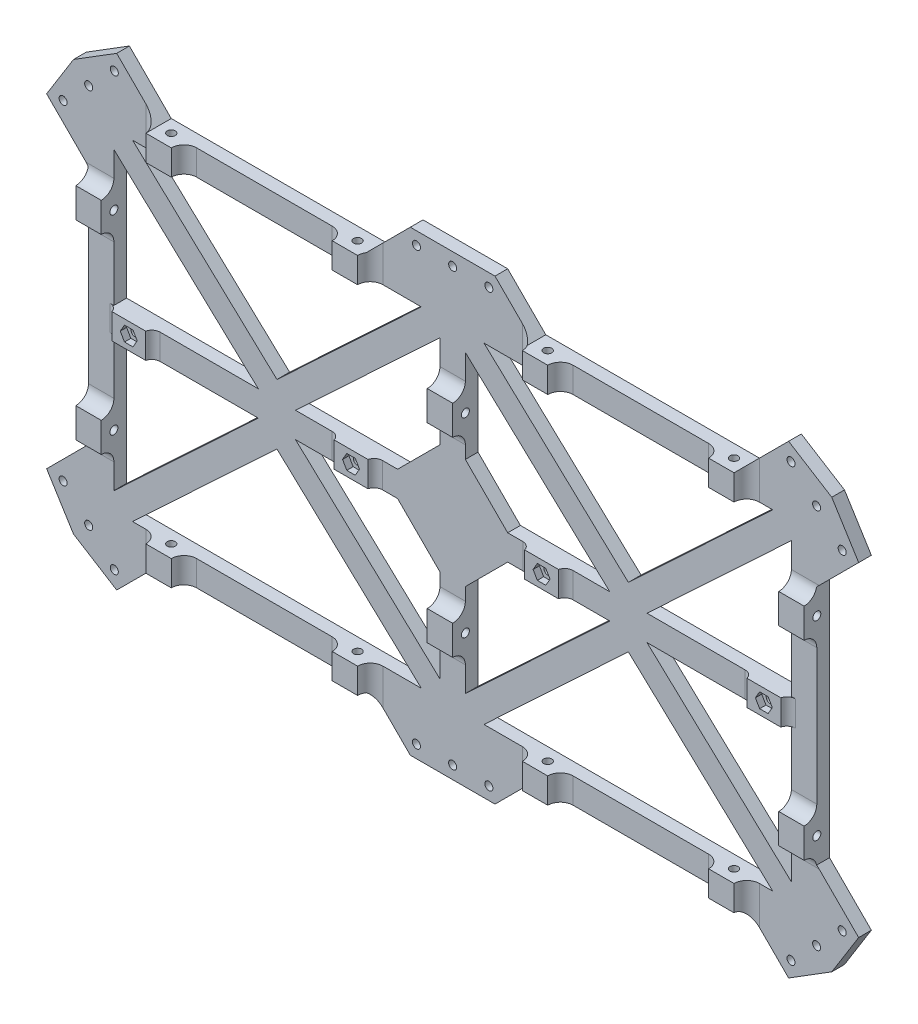
SolidWorks part; units mm, degrees
ref_plane "Plan de face" through (0, 0, 0) normal (0, 0, 1) x (1, 0, 0)
ref_plane "Plan de dessus" through (0, 0, 0) normal (0, 1, 0) x (1, 0, 0)
ref_plane "Plan de droite" through (0, 0, 0) normal (1, 0, 0) x (0, 0, -1)
sketch "Esquisse1" plane through (0, 0, 0) normal (0, 0, 1) x (1, 0, 0)
  line L0 (-86, 45) -> (86, 45)
  line L1 (-75.6076, 39) -> (-7.3924, 39)
  line L2 (-80, 34.8928) -> (-80, 3)
  line L3 (-75.6076, -39) -> (-7.3924, -39)
  line L4 (80, 34.8928) -> (80, 3)
  line L5 (86, 45) -> (86, -45)
  line L6 (-86, -45) -> (86, -45)
  line L7 (-86, 45) -> (-86, -45)
  line L8 (-80, 0) -> (80, 0) construction
  line L9 (-80, 3) -> (-45.8924, 3)
  line L10 (-3, -34.8928) -> (-3, -3)
  line L11 (0, 39) -> (0, -39) construction
  line L12 (-3, 34.8928) -> (-3, 3)
  line L13 (-37.1076, -3) -> (-3, -3)
  line L14 (-10, 45) -> (-10, 39) construction
  line L15 (10, 45) -> (10, 39) construction
  line L16 (-80, 39) -> (-41.5, 3) construction
  line L17 (-60.75, 21) -> (-58.701, 23.1913) construction
  line L18 (-58.701, 23.1913) -> (-75.6076, 39)
  line L19 (-80, -3) -> (-45.8924, -3)
  line L20 (-60.75, -21) -> (-62.799, -18.8087) construction
  line L21 (-60.75, -21) -> (-58.701, -23.1913) construction
  line L22 (-80, -39) -> (-41.5, -3) construction
  line L23 (-58.8571, 23.3372) -> (-41.5, 7.1072)
  line L24 (-60.75, 21) -> (-62.799, 18.8087) construction
  line L25 (-62.799, 18.8087) -> (-80, 34.8928)
  line L26 (-62.799, 18.8087) -> (-45.8924, 3)
  line L27 (-37.1076, 3) -> (-3, 3)
  line L28 (-62.799, -18.8087) -> (-45.8924, -3)
  line L29 (-62.799, -18.8087) -> (-80, -34.8928)
  line L30 (-58.8571, -23.3372) -> (-41.5, -7.1072)
  line L31 (-58.701, -23.1913) -> (-75.6076, -39)
  line L32 (3, 34.8928) -> (3, 3)
  line L33 (3, -34.8928) -> (3, -3)
  line L34 (80, -39) -> (41.5, -3) construction
  line L35 (60.75, -21) -> (58.701, -23.1913) construction
  line L36 (60.75, -21) -> (62.799, -18.8087) construction
  line L37 (58.701, -23.1913) -> (75.6076, -39)
  line L38 (58.8571, -23.3372) -> (41.5, -7.1072)
  line L39 (62.799, -18.8087) -> (80, -34.8928)
  line L40 (62.799, -18.8087) -> (45.8924, -3)
  line L41 (80, -3) -> (45.8924, -3)
  line L42 (37.1076, -3) -> (3, -3)
  line L43 (37.1076, 3) -> (3, 3)
  line L44 (80, 3) -> (45.8924, 3)
  line L45 (60.75, 21) -> (62.799, 18.8087) construction
  line L46 (60.75, 21) -> (58.701, 23.1913) construction
  line L47 (80, 39) -> (41.5, 3) construction
  line L48 (62.799, 18.8087) -> (45.8924, 3)
  line L49 (62.799, 18.8087) -> (80, 34.8928)
  line L50 (58.8571, 23.3372) -> (41.5, 7.1072)
  line L51 (58.701, 23.1913) -> (75.6076, 39)
  line L52 (7.3924, -39) -> (75.6076, -39)
  line L53 (7.3924, 39) -> (75.6076, 39)
  line L54 (-80, -39) -> (80, -39) construction
  line L55 (-80, -3) -> (-80, -34.8928)
  line L56 (-80, 39) -> (80, 39) construction
  line L57 (80, -3) -> (80, -34.8928)
  line L58 (-80, 39) -> (-80, -39) construction
  line L59 (-3, 39) -> (-41.5, 3) construction
  line L60 (80, 39) -> (80, -39) construction
  line L61 (-36.5997, 7.5821) -> (-34.5507, 5.3908) construction
  line L62 (-36.5997, 7.5821) -> (-38.6487, 9.7734) construction
  line L63 (-34.5507, 5.3908) -> (-3, 34.8928)
  line L64 (-34.5507, 5.3908) -> (-37.1076, 3)
  line L65 (-34.5507, 5.3908) -> (-37.1076, 3)
  line L66 (-34.5507, 5.3908) -> (-37.1076, 3)
  line L67 (-41.5, -3) -> (-3, -39) construction
  line L68 (-41.5, 7.1072) -> (-7.3924, 39)
  line L69 (-37.1076, -3) -> (-3, -34.8928)
  line L70 (41.5, -3) -> (3, -39) construction
  line L71 (41.5, -7.1072) -> (7.3924, -39)
  line L72 (-41.5, -7.1072) -> (-7.3924, -39)
  line L73 (37.1076, -3) -> (3, -34.8928)
  line L74 (3, 39) -> (41.5, 3) construction
  line L75 (41.5, 7.1072) -> (7.3924, 39)
  line L76 (34.5507, 5.3908) -> (3, 34.8928)
  line L77 (34.5507, 5.3908) -> (37.1076, 3)
  dimension "D6" = 3
  dimension "D1" = 78
  dimension "D2" = 160
  dimension "D3" = 80
  dimension "D4" = 39
  dimension "D7" = 3
  dimension "D8" = 3
  dimension "D9" = 3
  dimension "D10" = 10
  dimension "D11" = 10
  dimension "D12" = 3
  dimension "D13" = 38.5
  dimension "D14" = 3
  dimension "D15" = 3
  dimension "D5" = 6
extrude "Boss.-Extru.1" add sketch "Esquisse1" along normal blind 3 contours L0 L7 L6 L5 L55 L19 L28 L29 L52 L33 L42 L38 L37 L31 L30 L13 L10 L3 L27 L23 L18 L1 L12 L25 L26 L9 L2 L48 L49 L4 L44 L32 L53 L51 L50 L43 L41 L57 L39 region at (0, 0, 0)
sketch "Esquisse2" plane through (0, 0, 3) normal (0, 0, 1) x (1, 0, 0)
  line L0 (-13, -3) -> (-3, -13)
  line L1 (-37.1076, -3) -> (-3, -3) construction
  line L2 (-3, -34.8928) -> (-3, -3) construction
  line L3 (-13, -3) -> (-13, 3)
  line L4 (-37.1076, 3) -> (-3, 3) construction
  line L5 (-13, 3) -> (-3, 13)
  line L6 (-3, 34.8928) -> (-3, 3) construction
  line L7 (-3, 13) -> (3, 13)
  line L8 (3, 34.8928) -> (3, 3) construction
  line L9 (3, 13) -> (13, 3)
  line L10 (37.1076, 3) -> (3, 3) construction
  line L11 (13, 3) -> (13, -3)
  line L12 (37.1076, -3) -> (3, -3) construction
  line L13 (13, -3) -> (3, -13)
  line L14 (3, -34.8928) -> (3, -3) construction
  line L15 (3, -13) -> (-3, -13)
  line L16 (0, 45) -> (0, -45) construction
  line L17 (-86, 45) -> (86, 45) construction
  line L18 (-86, -45) -> (86, -45) construction
  line L19 (-10.3, 45) -> (-10.3, 39)
  line L20 (-75.6076, 39) -> (-7.3924, 39) construction
  line L21 (10.3, 45) -> (10.3, 39)
  line L22 (7.3924, 39) -> (75.6076, 39) construction
  line L23 (0, 45) -> (0, 54) construction
  line L24 (-11.55, 39) -> (-11.55, 45) construction
  line L25 (0, 54) -> (-10, 54)
  line L26 (0, 54) -> (10, 54)
  line L27 (10, 54) -> (19, 45)
  line L28 (-10, 54) -> (-19, 45)
  line L29 (-86, 0) -> (86, 0) construction
  line L30 (-86, 45) -> (-86, -45) construction
  line L31 (86, 45) -> (86, -45) construction
  line L32 (10, -54) -> (19, -45)
  line L33 (-10, -54) -> (-19, -45)
  line L34 (0, -54) -> (10, -54)
  line L35 (0, -54) -> (-10, -54)
  line L36 (-86, 45) -> (-110.1085, 69.1085) construction
  line L37 (-85.9542, 44.9542) -> (-99.2144, 31.694) construction
  line L38 (-85.9542, 44.9542) -> (-79.9085, 51) construction
  line L39 (-79.3417, 54.888) -> (-69.4537, 45)
  line L40 (-89.5355, 48.5355) -> (-79.3417, 54.888)
  line L41 (-95.888, 38.3417) -> (-86, 28.4537)
  line L42 (-89.5355, 48.5355) -> (-95.888, 38.3417)
  line L43 (79.3417, 54.888) -> (69.4537, 45)
  line L44 (89.5355, 48.5355) -> (79.3417, 54.888)
  line L45 (89.5355, 48.5355) -> (95.888, 38.3417)
  line L46 (95.888, 38.3417) -> (86, 28.4537)
  line L47 (95.888, -38.3417) -> (86, -28.4537)
  line L48 (89.5355, -48.5355) -> (95.888, -38.3417)
  line L49 (89.5355, -48.5355) -> (79.3417, -54.888)
  line L50 (79.3417, -54.888) -> (69.4537, -45)
  line L51 (-79.3417, -54.888) -> (-69.4537, -45)
  line L52 (-89.5355, -48.5355) -> (-79.3417, -54.888)
  line L53 (-89.5355, -48.5355) -> (-95.888, -38.3417)
  line L54 (-95.888, -38.3417) -> (-86, -28.4537)
  circle A0 centre (8.55, 51) radius 0.95
  circle A1 centre (-8.55, 51) radius 0.95
  circle A2 centre (0, 51) radius 0.95
  circle A3 centre (8.55, -51) radius 0.95
  circle A4 centre (-8.55, -51) radius 0.95
  circle A5 centre (0, -51) radius 0.95
  circle A6 centre (-85.9542, 44.9542) radius 0.95
  circle A7 centre (-92, 38.9085) radius 0.95
  circle A8 centre (-79.9085, 51) radius 0.95
  circle A9 centre (79.9085, 51) radius 0.95
  circle A10 centre (92, 38.9085) radius 0.95
  circle A11 centre (85.9542, 44.9542) radius 0.95
  circle A12 centre (92, -38.9085) radius 0.95
  circle A13 centre (85.9542, -44.9542) radius 0.95
  circle A14 centre (79.9085, -51) radius 0.95
  circle A15 centre (-79.9085, -51) radius 0.95
  circle A16 centre (-85.9542, -44.9542) radius 0.95
  circle A17 centre (-92, -38.9085) radius 0.95
  point P36 (-10.3, 42)
  line M19 (3, -34.8928) -> (3, -3)
  line M20 (3, -3) -> (37.1076, -3)
  line M23 (-37.1076, -3) -> (-3, -3)
  line M24 (-3, -3) -> (-3, -34.8928)
  line M26 (-3, 3) -> (-37.1076, 3)
  line M29 (-3, 34.8928) -> (-3, 3)
  line M30 (86, 45) -> (-86, 45)
  line M31 (-86, 45) -> (-86, -45)
  line M32 (-86, -45) -> (86, -45)
  line M33 (86, -45) -> (86, 45)
  line M40 (3, 3) -> (3, 34.8928)
  line M43 (37.1076, 3) -> (3, 3)
  dimension "D5" = 1.75
  dimension "D6" = 1.9
  dimension "D7" = 1.9
  dimension "D11" = 1.9
  dimension "D23" = 8.55
  dimension "D24" = 1.9
  dimension "D25" = 1.9
  dimension "D27" = 1.9
  dimension "D28" = 90
  dimension "D1" = 10
  dimension "D2" = 10
  dimension "D3" = 10.3
  dimension "D4" = 10.3
  dimension "D8" = 1.75
  dimension "D9" = 3
  dimension "D10" = 3
  dimension "D12" = 3
  dimension "D13" = 9
  dimension "D14" = 3
  dimension "D15" = 10
  dimension "D16" = 10
  dimension "D17" = 45
  dimension "D18" = 45
  dimension "D19" = 135
  dimension "D20" = 90
  dimension "D21" = 3
  dimension "D22" = 8.55
  dimension "D26" = 8.55
  dimension "D29" = 45
  dimension "D30" = 3.15
  dimension "D31" = 0
  dimension "D32" = 5
extrude "Boss.-Extru.2" add sketch "Esquisse2" against normal up to surface (3 mm away) contours A6 L39 L40 L42 L41 A8 A7 M30 M31 | L25 L28 L27 L26 A2 A1 A0 M30 | A11 L46 L45 L44 L43 A9 A10 M30 M33 | A13 L50 L49 L48 L47 A14 A12 M32 M33 | L35 L34 L32 L33 A4 A3 A5 M32 | A16 L54 L53 L52 L51 A15 A17 M32 M31 | L0 M23 M24 | L13 M20 M19 | L9 M40 M43 | L5 M26 M29 region at (-6.3333, -6.3333, 3) region at (-6.3333, 6.3333, 3) region at (6.3333, -6.3333, 3) region at (6.3333, 6.3333, 3) region at (0, 48.9683, 3) region at (-77.2295, 45.3738, 3) region at (74.6621, 49.6797, 3) region at (-86.3738, -36.2295, 3) region at (90.6797, -33.6621, 3) region at (0, -48.9683, 3) up to face at (41.5, -28.3691, 0)
sketch "Esquisse3" plane through (0, 0, 3) normal (0, 0, 1) x (1, 0, 0)
  line L0 (0, 54) -> (0, -54) construction
  line L1 (-86, 0) -> (86, 0) construction
  circle A0 centre (-85.9542, 44.9542) radius 0.95
  circle A1 centre (85.9542, 44.9542) radius 0.95
  circle A2 centre (85.9542, -44.9542) radius 0.95
  circle A3 centre (-85.9542, -44.9542) radius 0.95
  dimension "D1" = 1.9
extrude "Enlèv. mat.-Extru.1" cut sketch "Esquisse3" against normal up to surface (3 mm away) up to face at (-14.0269, -13.4732, 0)
sketch "Esquisse4" plane through (0, 0, 3) normal (0, 0, 1) x (1, 0, 0)
  line L0 (-86, 28.4537) -> (-86, -28.4537) construction
  line L1 (-80, 3) -> (-45.8924, 3) construction
  line L2 (-37.1076, 3) -> (-13, 3) construction
  line L3 (0, 54) -> (0, -54) construction
  circle A0 centre (-22.5, 0) radius 0.95
  circle A1 centre (-75, 0) radius 0.95
  circle A2 centre (22.5, 0) radius 0.95
  circle A3 centre (75, 0) radius 0.95
  dimension "D1" = 52.5
  dimension "D2" = 1.9
  dimension "D3" = 1.9
  dimension "D4" = 11
  dimension "D5" = 3
  dimension "D6" = 3
extrude "Enlèv. mat.-Extru.2" cut sketch "Esquisse4" against normal up to next
sketch "Esquisse5" plane through (0, 0, 3) normal (0, 0, 1) x (1, 0, 0)
  line L0 (-22.5, 0.95) -> (-22.5, -0.95) construction
  line L1 (0, 54) -> (0, -54) construction
  line L2 (-75, 0.95) -> (-75, -0.95) construction
  line L3 (-80, 3) -> (-45.8924, 3) construction
  line L4 (-73, 0) -> (-74, 1.7321)
  line L5 (-20.5, 0) -> (-21.5, 1.7321)
  line L6 (-21.5, 1.7321) -> (-23.5, 1.7321)
  line L7 (-23.5, 1.7321) -> (-24.5, 0)
  line L8 (-24.5, 0) -> (-23.5, -1.7321)
  line L9 (-74, 1.7321) -> (-76, 1.7321)
  line L10 (-23.5, -1.7321) -> (-21.5, -1.7321)
  line L11 (-21.5, -1.7321) -> (-20.5, 0)
  line L12 (-37.1076, 3) -> (-13, 3) construction
  line L13 (-26.5, 3) -> (-18.5, 3)
  line L14 (-26.5, 3) -> (-26.5, -3)
  line L15 (-26.5, -3) -> (-18.5, -3)
  line L16 (-18.5, 3) -> (-18.5, -3)
  line L17 (-37.1076, -3) -> (-13, -3) construction
  line L18 (-76, 1.7321) -> (-77, 0)
  line L19 (-77, 0) -> (-76, -1.7321)
  line L20 (-76, -1.7321) -> (-74, -1.7321)
  line L21 (-74, -1.7321) -> (-73, 0)
  line L22 (-80, -3) -> (-45.8924, -3) construction
  line L23 (-79, 3) -> (-71, 3)
  line L24 (-79, 3) -> (-79, -3)
  line L25 (-79, -3) -> (-71, -3)
  line L26 (-71, 3) -> (-71, -3)
  line L27 (22.5, 0.95) -> (22.5, -0.95) construction
  line L28 (18.5, 3) -> (18.5, -3)
  line L29 (26.5, -3) -> (18.5, -3)
  line L30 (26.5, 3) -> (26.5, -3)
  line L31 (26.5, 3) -> (18.5, 3)
  line L32 (21.5, -1.7321) -> (20.5, 0)
  line L33 (23.5, -1.7321) -> (21.5, -1.7321)
  line L34 (24.5, 0) -> (23.5, -1.7321)
  line L35 (23.5, 1.7321) -> (24.5, 0)
  line L36 (21.5, 1.7321) -> (23.5, 1.7321)
  line L37 (20.5, 0) -> (21.5, 1.7321)
  line L38 (75, 0.95) -> (75, -0.95) construction
  line L39 (71, 3) -> (71, -3)
  line L40 (79, -3) -> (71, -3)
  line L41 (79, 3) -> (79, -3)
  line L42 (79, 3) -> (71, 3)
  line L43 (74, -1.7321) -> (73, 0)
  line L44 (76, -1.7321) -> (74, -1.7321)
  line L45 (77, 0) -> (76, -1.7321)
  line L46 (76, 1.7321) -> (77, 0)
  line L47 (74, 1.7321) -> (76, 1.7321)
  line L48 (73, 0) -> (74, 1.7321)
  circle A0 centre (-22.5, 0) radius 0.95 construction
  circle A1 centre (-75, 0) radius 1.7321 construction
  circle A2 centre (-22.5, 0) radius 1.7321 construction
  circle A3 centre (-75, 0) radius 0.95 construction
  circle A4 centre (22.5, 0) radius 1.7321 construction
  circle A5 centre (75, 0) radius 1.7321 construction
  dimension "D1" = 4
  dimension "D2" = 2
  dimension "D3" = 2
  dimension "D4" = 4
  dimension "D5" = 4
  dimension "D6" = 4
extrude "Boss.-Extru.3" add sketch "Esquisse5" along normal blind 1.5
fillet "Congé1" radius 2 8 edges at (18.5, 0, 3) (71, 0, 3) (26.5, 0, 3) (79, 0, 3) (-18.5, 0, 3) (-26.5, 0, 3) (-71, 0, 3) (-79, 0, 3)
sketch "Esquisse6" plane through (0, 0, 3) normal (0, 0, 1) x (1, 0, 0)
  line L0 (-86, 0) -> (86, 0) construction
  line L1 (-86, 28.4537) -> (-86, -28.4537) construction
  line L2 (-86, -19) -> (-80, -19)
  line L4 (-80, -3) -> (-80, -34.8928) construction
  line L5 (-86, -19) -> (-86, -26)
  line L6 (-86, -26) -> (-80, -26)
  line L7 (-80, -26) -> (-80, -19)
  line L8 (-80, 26) -> (-80, 19)
  line L9 (-86, 26) -> (-80, 26)
  line L10 (-86, 19) -> (-86, 26)
  line L11 (-86, 19) -> (-80, 19)
  line L12 (0, 54) -> (0, -54) construction
  line L13 (80, -26) -> (80, -19)
  line L14 (86, -26) -> (80, -26)
  line L15 (86, -19) -> (86, -26)
  line L16 (86, -19) -> (80, -19)
  line L17 (86, 19) -> (80, 19)
  line L18 (86, 19) -> (86, 26)
  line L19 (86, 26) -> (80, 26)
  line L20 (80, 26) -> (80, 19)
  line L21 (-69.4537, 45) -> (-19, 45) construction
  line L22 (-69.4537, 45) -> (-63.4537, 45)
  line L23 (-69.4537, 45) -> (-69.4537, 39)
  line L24 (-69.4537, 39) -> (-63.4537, 39)
  line L25 (-63.4537, 45) -> (-63.4537, 39)
  line L26 (-75.6076, 39) -> (-7.3924, 39) construction
  line L27 (19.4537, 45) -> (19.4537, 39)
  line L28 (-25.4537, 45) -> (-19.4537, 45)
  line L29 (-25.4537, 45) -> (-25.4537, 39)
  line L30 (-25.4537, 39) -> (-19.4537, 39)
  line L31 (-19.4537, 45) -> (-19.4537, 39)
  line L32 (25.4537, 39) -> (19.4537, 39)
  line L33 (25.4537, 45) -> (25.4537, 39)
  line L34 (25.4537, 45) -> (19.4537, 45)
  line L35 (63.4537, 45) -> (63.4537, 39)
  line L36 (69.4537, 39) -> (63.4537, 39)
  line L37 (69.4537, 45) -> (69.4537, 39)
  line L38 (69.4537, 45) -> (63.4537, 45)
  line L39 (69.4537, -45) -> (63.4537, -45)
  line L40 (69.4537, -45) -> (69.4537, -39)
  line L41 (69.4537, -39) -> (63.4537, -39)
  line L42 (63.4537, -45) -> (63.4537, -39)
  line L43 (25.4537, -45) -> (19.4537, -45)
  line L44 (25.4537, -45) -> (25.4537, -39)
  line L45 (25.4537, -39) -> (19.4537, -39)
  line L46 (-19.4537, -45) -> (-19.4537, -39)
  line L47 (-25.4537, -39) -> (-19.4537, -39)
  line L48 (-25.4537, -45) -> (-25.4537, -39)
  line L49 (-25.4537, -45) -> (-19.4537, -45)
  line L50 (19.4537, -45) -> (19.4537, -39)
  line L51 (-63.4537, -45) -> (-63.4537, -39)
  line L52 (-69.4537, -39) -> (-63.4537, -39)
  line L53 (-69.4537, -45) -> (-69.4537, -39)
  line L54 (-69.4537, -45) -> (-63.4537, -45)
  line L55 (-3, 34.8928) -> (-3, 13) construction
  line L56 (-3, 26) -> (3, 26)
  line L57 (-3, 26) -> (-3, 19)
  line L58 (-3, 19) -> (3, 19)
  line L59 (3, 26) -> (3, 19)
  line L60 (3, 34.8928) -> (3, 13) construction
  line L61 (-3, -34.8928) -> (-3, -13) construction
  line L62 (-3, -26) -> (3, -26)
  line L63 (-3, -26) -> (-3, -19)
  line L64 (-3, -19) -> (3, -19)
  line L65 (3, -26) -> (3, -19)
  line L66 (3, -34.8928) -> (3, -13) construction
  dimension "D1" = 19
  dimension "D2" = 7
  dimension "D3" = 6
  dimension "D4" = 6
  dimension "D5" = 38
  dimension "D6" = 0
  dimension "D7" = 7
  dimension "D8" = 7
extrude "Boss.-Extru.4" add sketch "Esquisse6" along normal blind 3
sketch "Esquisse7" plane through (0, -45, 0) normal (0, -1, 0) x (1, 0, 0)
  line L0 (-69.4537, 0) -> (-63.4537, 6) construction
  line L1 (-25.4537, 6) -> (-25.4537, 0) construction
  line L2 (-25.4537, 6) -> (-25.4537, 3) construction
  line L3 (-69.4537, 0) -> (-19, 0) construction
  line L4 (-25.4537, 0) -> (-19.4537, 6) construction
  line L5 (25.4537, 6) -> (25.4537, 0) construction
  line L6 (19, 0) -> (69.4537, 0) construction
  line L7 (19.4537, 6) -> (25.4537, 0) construction
  line L8 (69.4537, 0) -> (63.4537, 6) construction
  circle A0 centre (-66.4537, 3) radius 0.95
  circle A1 centre (-22.4537, 3) radius 0.95
  circle A2 centre (22.4537, 3) radius 0.95
  circle A3 centre (66.4537, 3) radius 0.95
  dimension "D1" = 1.9
  dimension "D2" = 1.9
  dimension "D3" = 1.9
  dimension "D4" = 1.9
extrude "Enlèv. mat.-Extru.3" cut sketch "Esquisse7" against normal up to next
sketch "Esquisse8" plane through (0, 45, 0) normal (0, 1, 0) x (1, 0, 0)
  line L0 (-63.4537, -6) -> (-69.4537, 0) construction
  line L1 (-25.4537, -6) -> (-25.4537, 0) construction
  line L2 (-69.4537, 0) -> (-19, 0) construction
  line L3 (-25.4537, 0) -> (-19.4537, -6) construction
  line L4 (19.4537, -6) -> (19.4537, 0) construction
  line L5 (19, 0) -> (69.4537, 0) construction
  line L6 (19.4537, 0) -> (25.4537, -6) construction
  line L7 (63.4537, -6) -> (69.4537, 0) construction
  circle A0 centre (66.4537, -3) radius 0.95
  circle A1 centre (22.4537, -3) radius 0.95
  circle A2 centre (-22.4537, -3) radius 0.95
  circle A3 centre (-66.4537, -3) radius 0.95
  dimension "D1" = 1.9
  dimension "D2" = 1.9
  dimension "D3" = 1.9
  dimension "D4" = 1.9
extrude "Enlèv. mat.-Extru.4" cut sketch "Esquisse8" against normal up to next
fillet "Congé2" radius 3 28 edges at (-83, -19, 3) (-83, -26, 3) (-83, 19, 3) (-83, 26, 3) (-63.4537, 42, 3) (-69.4537, 42, 3) (-25.4537, 42, 3) (-19.4537, 42, 3) (25.4537, 42, 3) (19.4537, 42, 3) (63.4537, 42, 3) (69.4537, 42, 3) (83, 19, 3) (83, 26, 3) (83, -19, 3) (83, -26, 3) (69.4537, -42, 3) (63.4537, -42, 3) (25.4537, -42, 3) (19.4537, -42, 3) (-19.4537, -42, 3) (-25.4537, -42, 3) (-63.4537, -42, 3) (-69.4537, -42, 3) (0, 19, 3) (0, 26, 3) (0, -19, 3) (0, -26, 3)
sketch "Esquisse9" plane through (-86, 0, 0) normal (-1, 0, 0) x (0, 0, 1)
  line L0 (6, 26) -> (0, 26) construction
  line L1 (0, 28.4537) -> (0, -28.4537) construction
  line L2 (0, 26) -> (6, 19) construction
  line L3 (6, -19) -> (0, -19) construction
  line L4 (0, -19) -> (6, -26) construction
  arc A0 (3, -16) -> (6, -19) centre (6, -16) ccw construction
  circle A1 centre (3, -22.5) radius 0.95
  circle A2 centre (3, 22.5) radius 0.95
  dimension "D1" = 1.9
  dimension "D2" = 1.9
extrude "Enlèv. mat.-Extru.5" cut sketch "Esquisse9" against normal up to next
sketch "Esquisse10" plane through (-3, 0, 0) normal (-1, 0, 0) x (0, 0, 1)
  line L0 (6, 26) -> (0, 26) construction
  line L2 (0, 26) -> (6, 19) construction
  line L3 (6, -19) -> (0, -19) construction
  line L4 (0, -34.8928) -> (0, -13) construction
  line L5 (0, -19) -> (6, -26) construction
  line L6 (0, 34.8928) -> (0, 13) construction
  arc A0 (3, 29) -> (6, 26) centre (6, 29) ccw construction
  circle A1 centre (3, -22.5) radius 0.95
  circle A2 centre (3, 22.5) radius 0.95
  dimension "D1" = 1.9
  dimension "D2" = 1.9
extrude "Enlèv. mat.-Extru.6" cut sketch "Esquisse10" against normal up to next
sketch "Esquisse11" plane through (80, 0, 0) normal (-1, 0, 0) x (0, 0, 1)
  line L0 (6, -19) -> (0, -18.9464) construction
  line L1 (0, -3) -> (0, -34.8928) construction
  line L2 (0, -18.9464) -> (6, -26) construction
  line L3 (6, 26) -> (0, 26) construction
  line L4 (0, 34.8928) -> (0, 3) construction
  line L5 (0, 26) -> (6, 19) construction
  circle A0 centre (3, 22.5) radius 0.95
  circle A1 centre (3, -22.4732) radius 0.95
  dimension "D1" = 1.9
  dimension "D2" = 1.9
extrude "Enlèv. mat.-Extru.7" cut sketch "Esquisse11" against normal up to next
